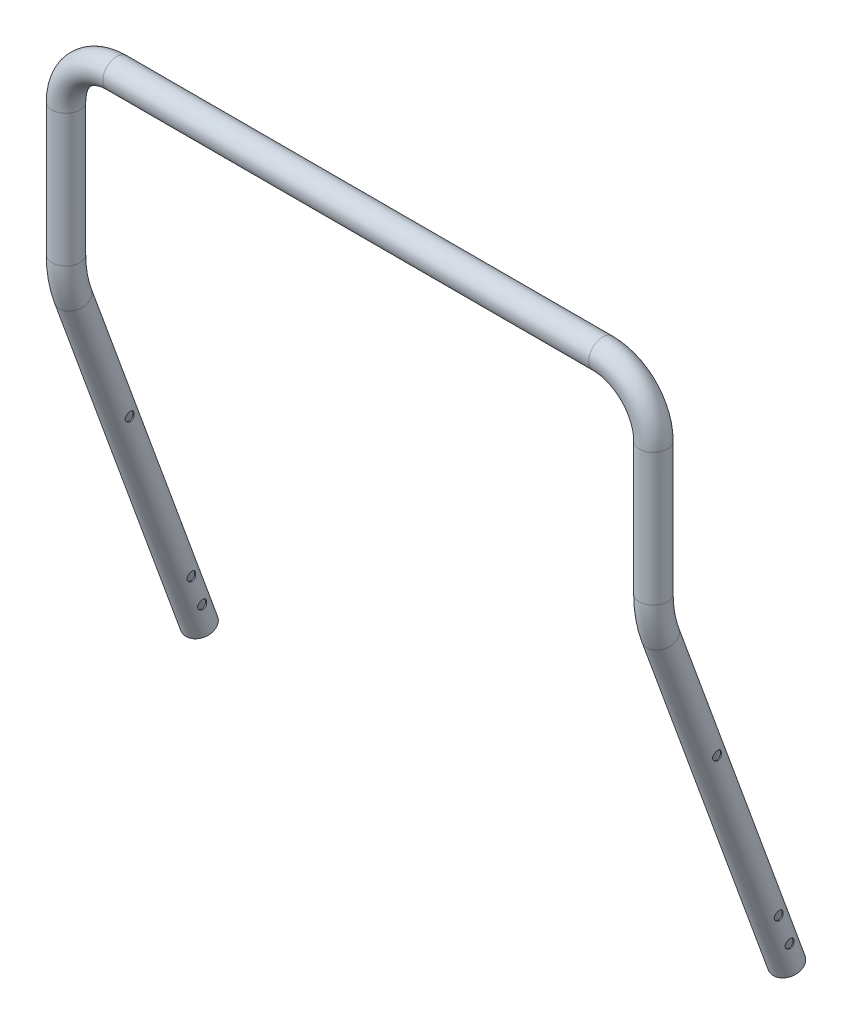
SolidWorks part; units mm, degrees
ref_plane "Front Plane" through (0, 0, 0) normal (0, 0, 1) x (1, 0, 0)
ref_plane "Top Plane" through (0, 0, 0) normal (0, 1, 0) x (1, 0, 0)
ref_plane "Right Plane" through (0, 0, 0) normal (1, 0, 0) x (0, 0, -1)
sketch "Sketch8" plane through (0, 0, 0) normal (0, 0, 1) x (1, 0, 0)
  line L0 (-191.5, 0) -> (191.5, 0)
  line L1 (-231.5, -40) -> (-231.5, -100)
  line L2 (231.5, -40) -> (231.5, -100)
  arc A0 (231.5, -40) -> (191.5, 0) centre (191.5, -40) ccw
  arc A1 (-191.5, 0) -> (-231.5, -40) centre (-191.5, -40) ccw
  point P4 (0, 0)
  point P9 (231.5, 0)
  point P12 (-231.5, 0)
  dimension "D2" = 40
  dimension "450" = 463
  dimension "D3" = 60
  dimension "D4" = 60
ref_plane "Plane3" through (231.5, -100, 0) normal (0, -1, 0) x (-1, 0, 0)
sketch "Sketch9" plane through (231.5, -100, 0) normal (0, -1, 0) x (-1, 0, 0)
  circle A0 centre (0, 0) radius 11
  circle A1 centre (0, 0) radius 10.2
  dimension "D1" = 0.8
ref_plane "Plane5" through (231.5, 0, 0) normal (1, 0, 0) x (0, 0, -1)
sketch "Sketch13" plane through (231.5, 0, 0) normal (1, 0, 0) x (0, 0, -1)
  line L0 (0, -100) -> (0, -144.2597)
  line L1 (-11, -100) -> (11, -100) construction
  line L2 (5.4277, -175.0415) -> (104.9678, -448.5257)
  arc A0 (5.4277, -175.0415) -> (0, -144.2597) centre (90, -144.2597) cw
  dimension "D1" = 90
  dimension "D2" = 160
sweep "Sweep2" add profiles "Sketch9" path "Sketch8"
sweep "Sweep3" add profiles "Sketch9<2>" path "Sketch13"
sketch "Sketch9<2>" plane through (231.5, -100, 0) normal (0, -1, 0) x (-1, 0, 0) same geometry as "Sketch9"
mirror "Mirror1" about plane through (0, 0, 0) normal (1, 0, 0) of "Sweep3"
sketch "Sketch14" plane through (231.5, 0, 0) normal (1, 0, 0) x (0, 0, -1)
  line L0 (104.9678, -448.5257) -> (5.4277, -175.0415) construction
  line L1 (94.6311, -452.2879) -> (115.3044, -444.7635) construction
  line L2 (15.7643, -171.2793) -> (-4.909, -178.8037) construction
  circle A0 centre (39.6596, -269.0931) radius 3.5
  circle A1 centre (88.2265, -402.5295) radius 3.5
  circle A3 centre (96.777, -426.0218) radius 3.5
  circle A4 centre (0, 0) radius 10.2 construction
  dimension "D1" = 142
  dimension "D2" = 25
  dimension "D3" = 272
extrude "Cut-Extrude1" cut sketch "Sketch14" against normal up to next and the other way up to next
mirror "Mirror2" about plane through (0, 0, 0) normal (1, 0, 0) of "Cut-Extrude1"
